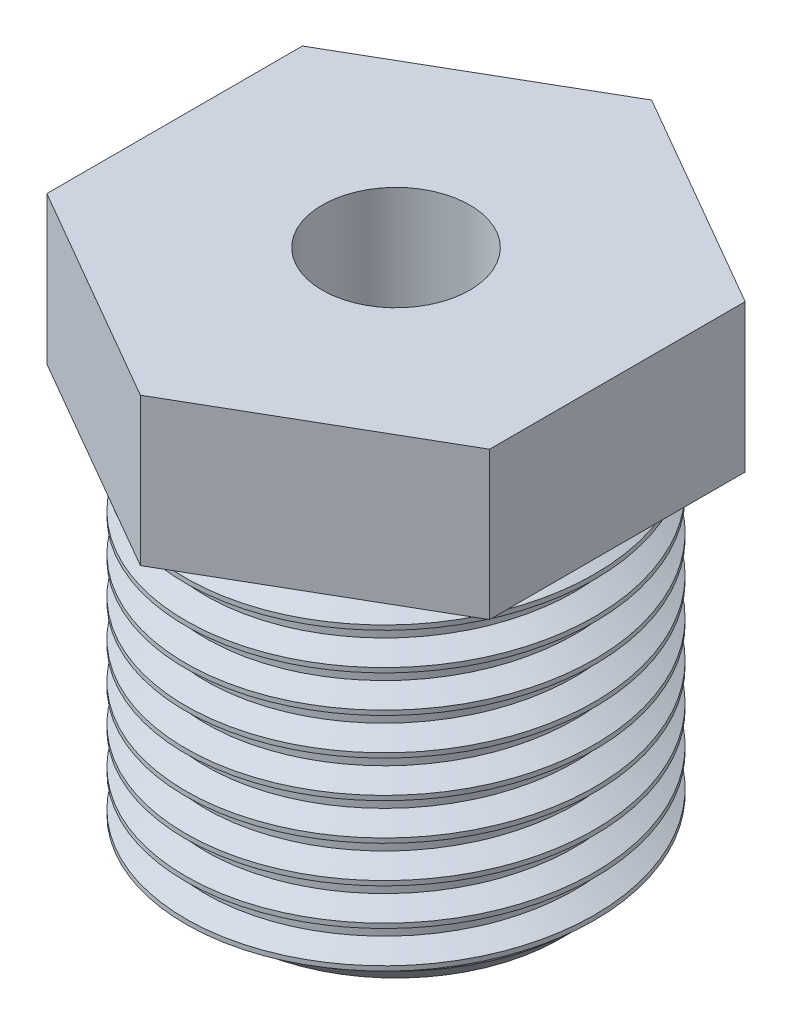
SolidWorks part; units mm, degrees
material "Aluminum Bronze"
ref_plane "Front Plane" through (0, 0, 0) normal (0, 0, 1) x (1, 0, 0)
ref_plane "Top Plane" through (0, 0, 0) normal (0, 1, 0) x (1, 0, 0)
ref_plane "Right Plane" through (0, 0, 0) normal (1, 0, 0) x (0, 0, -1)
sketch "Sketch1" plane through (0, 0, 0) normal (0, 1, 0) x (1, 0, 0)
  circle A0 centre (0, 0) radius 5
extrude "Boss-Extrude1" add sketch "Sketch1" along normal blind 10
chamfer "Chamfer1" distance 0.55 angle 45 1 edges at (0, 0, 5)
sketch "Sketch2" plane through (0, 10, 0) normal (0, 1, 0) x (1, 0, 0)
  line L1 (0, 6.9282) -> (-6, 3.4641)
  line L2 (-6, 3.4641) -> (-6, -3.4641)
  line L3 (-6, -3.4641) -> (0, -6.9282)
  line L4 (0, -6.9282) -> (6, -3.4641)
  line L5 (6, -3.4641) -> (6, 3.4641)
  line L6 (6, 3.4641) -> (0, 6.9282)
  circle A0 centre (0, 0) radius 6
  circle A1 centre (0, 0) radius 6 construction
  circle M3 centre (0, 0) radius 5
  dimension "D1" = 12
extrude "Boss-Extrude3" add sketch "Sketch2" along normal blind 4 contours A0 M3 | A0 L1 L2 | M3 | A0 L6 L1 | A0 L5 L6 | A0 L4 L5 | A0 L3 L4 | A0 L2 L3 region at (0, 10, -6.2014) region at (-5.3706, 10, -3.1007) region at (0, 10, -5.8303) region at (5.3706, 10, -3.1007) region at (-5.3706, 10, 3.1007) region at (5.3706, 10, 3.1007) region at (0, 10, 6.2014) region at (0, 10, 0)
sketch "Sketch5" plane through (0, 14, 0) normal (0, 1, 0) x (1, 0, 0)
  circle A0 centre (0, 0) radius 2
extrude "Cut-Extrude1" cut sketch "Sketch5" against normal through all both and the other way through all
thread "Thread1" pitch 1 method extrude profile "Thread Profile1" start angle 0, offset 0, length 9, pitch 1, diameter 10
ref_plane "Plane1" through (-5, 10, 0) normal (0, 0, 1) x (-1, 0, 0)
sketch "Thread Profile1" plane through (-5, 10, 0) normal (0, 0, 1) x (-1, 0, 0)
  line L0 (0, 0) -> (0, 1) construction
  line L1 (0, 0) -> (0.5413, 0.3125)
  line L2 (0.5413, 0.3125) -> (0.5413, 0.4375)
  line L3 (0.5413, 0.4375) -> (0, 0.75)
  line L4 (0.5413, 0.375) -> (0, 0.375) construction
  line L11 (0, 0) -> (0, 0.75)
  point P2 (0, 0)
  dimension "Pitch" = 1
  dimension "Profile_Angle" = 60
  dimension "Profile_Land" = 0.125
  dimension "Profile_Height" = 0.5413
